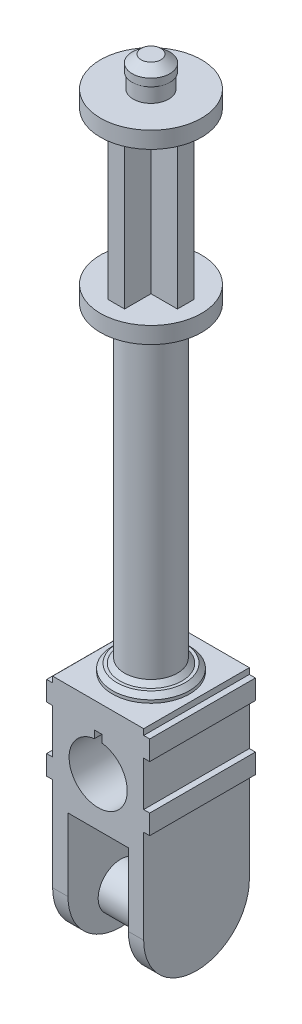
SolidWorks part; units mm, degrees
ref_plane "Front Plane" through (0, 0, 0) normal (0, 0, 1) x (1, 0, 0)
ref_plane "Top Plane" through (0, 0, 0) normal (0, 1, 0) x (1, 0, 0)
ref_plane "Right Plane" through (0, 0, 0) normal (1, 0, 0) x (0, 0, -1)
sketch "Sketch2" plane through (0, 0, 0) normal (0, 1, 0) x (1, 0, 0)
  line L1 (-3.015, -3.5) -> (3.015, -3.5)
  line L2 (-3.015, -3.5) -> (-3.015, 3.5)
  line L3 (-3.015, 3.5) -> (3.015, 3.5)
  line L4 (3.015, -3.5) -> (3.015, 3.5)
  line L5 (-3.015, -3.5) -> (3.015, 3.5) construction
  line L6 (-3.015, 3.5) -> (3.015, -3.5) construction
  point P0 (0, 0)
  dimension "D1" = 6.03
  dimension "D2" = 7
extrude "Boss-Extrude1" add sketch "Sketch2" along normal blind 15.64
sketch "Sketch3" plane through (0, 0, 0) normal (0, 0, 1) x (1, 0, 0)
  line L0 (-3.015, 0) -> (3.015, 0) construction
  line L1 (-2, 0) -> (2, 0)
  line L2 (-2, 0) -> (-2, 8.3)
  line L3 (-2, 8.3) -> (2, 8.3)
  line L4 (2, 0) -> (2, 8.3)
  line L5 (0, 0) -> (0, 3.4914) construction
  dimension "D1" = 8.3
  dimension "D2" = 4
extrude "Cut-Extrude1" cut sketch "Sketch3" against normal through all both and the other way through all
fillet "Fillet1" radius 3.5 4 edges at (-2.5075, 0, 3.5) (-2.5075, 0, -3.5) (2.5075, 0, -3.5) (2.5075, 0, 3.5)
sketch "Sketch4" plane through (-2, 0, 0) normal (1, 0, 0) x (0, 0, -1)
  line L0 (3.5, 8.3) -> (-3.5, 8.3) construction
  circle A0 centre (0, 2.4) radius 1.5
  dimension "D1" = 3
  dimension "D2" = 5.9
extrude "Boss-Extrude2" add sketch "Sketch4" along normal up to surface (4 mm away) up to face at (2, 4.4301, 0)
sketch "Sketch6" plane through (0, 0, -3.5) normal (0, 0, -1) x (-1, 0, 0)
  line L0 (-2, 8.3) -> (2, 8.3) construction
  line L1 (0, 11.525) -> (0, 12.4428) construction
  line L3 (-0.25, 13.4337) -> (-0.25, 13.9337)
  line L4 (-0.25, 13.9337) -> (0.25, 13.9337)
  line L5 (0.25, 13.9337) -> (0.25, 13.4337)
  arc A0 (-0.25, 13.4337) -> (0.25, 13.4337) centre (0, 11.525) ccw
  dimension "D1" = 3.85
  dimension "D2" = 3.225
  dimension "D3" = 0.5
  dimension "D4" = 0.5
extrude "Cut-Extrude2" cut sketch "Sketch6" against normal through all both and the other way through all
sketch "Sketch7" plane through (3.015, 0, 0) normal (1, 0, 0) x (0, 0, -1)
  line L0 (-3.5, 15.64) -> (-3.5, 3.5) construction
  line L1 (-3.5, 15.25) -> (3.5, 15.25)
  line L2 (-3.5, 15.25) -> (-3.5, 13.95)
  line L3 (-3.5, 13.95) -> (3.5, 13.95)
  line L4 (3.5, 15.25) -> (3.5, 13.95)
  line L5 (3.5, 15.64) -> (3.5, 3.5) construction
  line L7 (-3.5, 9.7) -> (3.5, 9.7)
  line L8 (-3.5, 9.7) -> (-3.5, 11)
  line L9 (-3.5, 11) -> (3.5, 11)
  line L10 (3.5, 9.7) -> (3.5, 11)
  dimension "D1" = 9.7
  dimension "D2" = 1.3
  dimension "D3" = 1.3
  dimension "D4" = 5.55
extrude "Boss-Extrude3" add sketch "Sketch7" along normal blind 0.4
mirror "Mirror1" about plane through (0, 0, 0) normal (1, 0, 0) of "Boss-Extrude3"
sketch "Sketch8" plane through (0, 15.64, 0) normal (0, 1, 0) x (1, 0, 0)
  circle A0 centre (0, 0) radius 1.75
  dimension "D1" = 3.5
extrude "Boss-Extrude4" add sketch "Sketch8" along normal blind 21.14
sketch "Sketch9" plane through (0, 36.78, 0) normal (0, 1, 0) x (1, 0, 0)
  circle A0 centre (0, 0) radius 3.35
  dimension "D1" = 6.7
extrude "Boss-Extrude5" add sketch "Sketch9" along normal blind 1.1
sketch "Sketch10" plane through (0, 37.88, 0) normal (0, 1, 0) x (1, 0, 0)
  line L0 (-0.55, 2.3) -> (-0.55, 0.55)
  line L1 (-0.55, -2.3) -> (0.55, -2.3)
  line L2 (-2.3, -0.55) -> (-2.3, 0.55)
  line L3 (-0.55, 2.3) -> (0.55, 2.3)
  line L4 (2.3, -0.55) -> (2.3, 0.55)
  line L5 (-0.55, -0.55) -> (0.55, 0.55) construction
  line L6 (-0.55, 0.55) -> (0.55, -0.55) construction
  line L7 (-0.55, 0.55) -> (-2.3, 0.55)
  line L8 (-2.3, -0.55) -> (-0.55, -0.55)
  line L9 (-0.55, -0.55) -> (-0.55, -2.3)
  line L10 (0.55, 2.3) -> (0.55, 0.55)
  line L11 (0.55, 0.55) -> (2.3, 0.55)
  line L12 (0.55, -2.3) -> (0.55, -0.55)
  line L13 (0.55, -0.55) -> (2.3, -0.55)
  point P0 (0, 0)
  dimension "D2" = 1.1
  dimension "D3" = 1.1
  dimension "D4" = 1.1
  dimension "D5" = 1.1
extrude "Boss-Extrude6" add sketch "Sketch10" along normal blind 10.1
sketch "Sketch11" plane through (0, 47.98, 0) normal (0, 1, 0) x (1, 0, 0)
  circle A0 centre (0, 0) radius 3.35
  dimension "D1" = 6.7
extrude "Boss-Extrude7" add sketch "Sketch11" along normal blind 1.1
sketch "Sketch12" plane through (0, 49.08, 0) normal (0, 1, 0) x (1, 0, 0)
  circle A0 centre (0, 0) radius 1.175
  dimension "D1" = 2.35
extrude "Boss-Extrude8" add sketch "Sketch12" along normal blind 1
sketch "Sketch13" plane through (0, 50.08, 0) normal (0, 1, 0) x (1, 0, 0)
  circle A0 centre (0, 0) radius 1.25
  dimension "D1" = 2.5
extrude "Boss-Extrude9" add sketch "Sketch13" along normal blind 1
chamfer "Chamfer1" distance 0.5 angle 50 1 edges at (0, 51.08, 1.25) first distance on face at (0, 51.08, 1.25)
sketch "Sketch14" plane through (0, 15.64, 0) normal (0, 1, 0) x (1, 0, 0)
  circle A0 centre (0, 0) radius 2.55
  dimension "D1" = 5.1
extrude "Boss-Extrude10" add sketch "Sketch14" along normal blind 0.5
chamfer "Chamfer3" distance 0.3 angle 45 2 edges at (0, 16.14, 2.55) (0, 16.14, 1.75)
